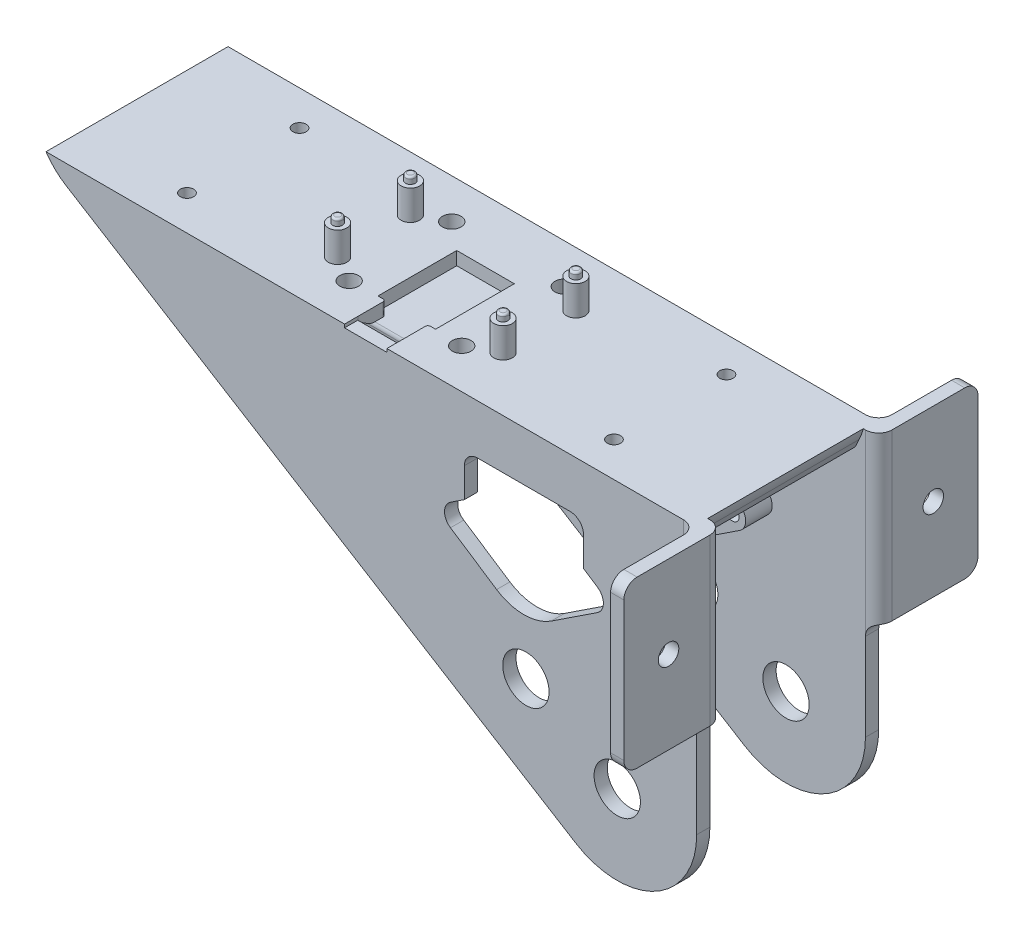
SolidWorks part; units mm, degrees
material "尼龙 101"
ref_plane "前视基准面" through (0, 0, 0) normal (0, 0, 1) x (1, 0, 0)
ref_plane "上视基准面" through (0, 0, 0) normal (0, 1, 0) x (1, 0, 0)
ref_plane "右视基准面" through (0, 0, 0) normal (1, 0, 0) x (0, 0, -1)
other "Configuration Table"
sketch "草图1" plane through (0, 0, 0) normal (0, 1, 0) x (1, 0, 0)
  line L1 (-50, 12.75) -> (50, 12.75)
  line L2 (-50, 12.75) -> (-50, -12.75)
  line L3 (-50, -12.75) -> (50, -12.75)
  line L4 (50, 12.75) -> (50, -12.75)
  line L5 (-50, 12.75) -> (50, -12.75) construction
  line L6 (-50, -12.75) -> (50, 12.75) construction
  point P0 (0, 0)
  dimension "D1" = 100
  dimension "D2" = 25.5
extrude "凸台-拉伸1" add sketch "草图1" along normal blind 3
sketch "草图2" plane through (0, 3, 0) normal (0, 1, 0) x (1, 0, 0)
  line L0 (0, 0) -> (0, 5.35) construction
  line L1 (-5.35, 5.35) -> (5.35, 5.35)
  line L2 (5.35, 5.35) -> (5.35, -7.55)
  line L3 (5.35, -7.55) -> (4.35, -7.55)
  line L4 (4.35, -7.55) -> (4.35, 4.35)
  line L5 (4.35, 4.35) -> (-4.35, 4.35)
  line L6 (-4.35, -7.55) -> (-4.35, 4.35)
  line L7 (-5.35, -7.55) -> (-4.35, -7.55)
  line L8 (-5.35, 5.35) -> (-5.35, -7.55)
  point P9 (0, 4.35)
  dimension "D1" = 8.7
  dimension "D2" = 11.9
  dimension "D3" = 4.35
  dimension "D4" = 1
  dimension "D5" = 1
extrude "凸台-拉伸2" add sketch "草图2" along normal blind 1.5
sketch "草图5" plane through (0, 3, 0) normal (0, 1, 0) x (1, 0, 0)
  line L0 (0, 12.75) -> (0, 0) construction
  line L1 (50, 12.75) -> (-50, 12.75) construction
  line L2 (0, 0) -> (50, 0) construction
  line L3 (50, -12.75) -> (50, 12.75) construction
  circle A0 centre (12.5, 5.5) radius 1.4
  circle A1 centre (12.5, -5.5) radius 1.4
  circle A2 centre (-12.5, -5.5) radius 1.4
  circle A3 centre (-12.5, 5.5) radius 1.4
  dimension "D1" = 2.8
  dimension "D2" = 25
  dimension "D3" = 11
extrude "凸台-拉伸3" add sketch "草图5" along normal blind 4.5
sketch "草图6" plane through (0, 7.5, 0) normal (0, 1, 0) x (1, 0, 0)
  circle A0 centre (-12.5, -5.5) radius 0.725
  circle A1 centre (-12.5, 5.5) radius 0.725
  circle A2 centre (12.5, 5.5) radius 0.725
  circle A3 centre (12.5, -5.5) radius 0.725
  dimension "D1" = 1.45
extrude "凸台-拉伸4" add sketch "草图6" along normal blind 1
sketch "草图7" plane through (0, 3, 0) normal (0, 1, 0) x (1, 0, 0)
  line L0 (0, 0) -> (0, 12.75) construction
  line L1 (50, 12.75) -> (-50, 12.75) construction
  line L2 (0, 0) -> (50, 0) construction
  line L3 (50, -12.75) -> (50, 12.75) construction
  circle A0 centre (32.25, 8.5) radius 1
  circle A1 centre (-32.25, 8.5) radius 1
  circle A2 centre (-32.25, -8.5) radius 1
  circle A3 centre (32.25, -8.5) radius 1
  dimension "D1" = 2
  dimension "D2" = 17
  dimension "D3" = 64.5
extrude "切除-拉伸1" cut sketch "草图7" against normal blind 10
sketch "草图8" plane through (0, 0, 0) normal (0, -1, 0) x (1, 0, 0)
  circle A0 centre (-32.25, 8.5) radius 2
  circle A1 centre (32.25, 8.5) radius 2
  circle A2 centre (32.25, -8.5) radius 2
  circle A3 centre (-32.25, -8.5) radius 2
  dimension "D1" = 4
extrude "切除-拉伸2" cut sketch "草图8" against normal blind 1
fillet "圆角1" radius 2 4 edges at (-50, 1.5, -12.75) (50, 1.5, -12.75) (-50, 1.5, 12.75) (50, 1.5, 12.75)
sketch "草图9" plane through (0, 3, 0) normal (0, 1, 0) x (1, 0, 0)
  line L0 (0, 12.75) -> (0, 0) construction
  line L1 (48, 12.75) -> (-48, 12.75) construction
  line L2 (0, 0) -> (50, 0) construction
  line L3 (50, -10.75) -> (50, 10.75) construction
  circle A0 centre (8.5, 7.75) radius 2.65
  circle A1 centre (-8.5, 7.75) radius 2.65
  circle A2 centre (-8.5, -7.75) radius 2.65
  circle A3 centre (8.5, -7.75) radius 2.65
  dimension "D1" = 17
  dimension "D2" = 15.5
  dimension "D3" = 5.3
extrude "凸台-拉伸5" add sketch "草图9" along normal blind 3.5
sketch "草图11" plane through (0, 6.5, 0) normal (0, 1, 0) x (1, 0, 0)
  circle A0 centre (-8.5, 7.75) radius 1.05
  circle A1 centre (-8.5, -7.75) radius 1.05
  circle A2 centre (8.5, -7.75) radius 1.05
  circle A3 centre (8.5, 7.75) radius 1.05
  dimension "D1" = 2.1
extrude "切除-拉伸4" cut sketch "草图11" against normal blind 100
sketch "草图12" plane through (0, 6.5, 0) normal (0, 1, 0) x (1, 0, 0)
  circle A0 centre (-8.5, 7.75) radius 1.41
  circle A1 centre (8.5, 7.75) radius 1.41
  circle A2 centre (-8.5, -7.75) radius 1.41
  circle A3 centre (8.5, -7.75) radius 1.41
  dimension "D1" = 2.82
extrude "切除-拉伸5" cut sketch "草图12" against normal blind 5.5
fillet "圆角2" radius 0.3 4 edges at (12.5, 8.5, -4.775) (12.5, 8.5, 6.225) (-12.5, 8.5, 6.225) (-12.5, 8.5, -4.775)
sketch "草图15" plane through (0, 3, 0) normal (0, 1, 0) x (1, 0, 0)
  line L0 (0, 0) -> (0, 12.75) construction
  line L1 (48, 12.75) -> (-48, 12.75) construction
  line L2 (-4.35, 4.35) -> (4.35, 4.35)
  line L3 (4.35, 4.35) -> (4.35, -7.55)
  line L4 (4.35, -7.55) -> (3.2, -7.55)
  line L5 (3.2, -7.55) -> (3.2, -12.75)
  line L6 (-48, -12.75) -> (48, -12.75) construction
  line L7 (3.2, -12.75) -> (-3.2, -12.75)
  line L8 (-3.2, -7.55) -> (-3.2, -12.75)
  line L9 (-4.35, -7.55) -> (-3.2, -7.55)
  line L10 (-4.35, 4.35) -> (-4.35, -7.55)
  line L11 (4.35, 4.35) -> (4.35, -7.55) construction
  point P14 (0, -12.75)
  point P17 (0, 4.35)
  dimension "D1" = 6.4
extrude "切除-拉伸8" cut sketch "草图15" against normal blind 2
sketch "草图17" plane through (0, 4.5, 0) normal (0, 1, 0) x (1, 0, 0)
  line L8 (-4.35, -7.55) -> (-4.35, 4.35)
  line L9 (-4.35, 4.35) -> (4.35, 4.35)
  line L10 (4.35, 4.35) -> (4.35, -7.55)
  line L11 (4.35, -7.55) -> (5.35, -7.55)
  line L12 (5.35, -7.55) -> (5.35, 5.35)
  line L13 (5.35, 5.35) -> (-5.35, 5.35)
  line L14 (-5.35, 5.35) -> (-5.35, -7.55)
  line L15 (-5.35, -7.55) -> (-4.35, -7.55)
  line L16 (-4.35, -7.55) -> (-4.35, 4.35)
  line L17 (-4.35, 4.35) -> (4.35, 4.35)
  line L18 (4.35, 4.35) -> (4.35, -7.55)
  line L19 (4.35, -7.55) -> (5.35, -7.55)
  line L20 (5.35, -7.55) -> (5.35, 5.35)
  line L21 (5.35, 5.35) -> (-5.35, 5.35)
  line L22 (-5.35, 5.35) -> (-5.35, -7.55)
  line L23 (-5.35, -7.55) -> (-4.35, -7.55)
  dimension "D1" = 0
extrude "切除-拉伸9" cut sketch "草图17" against normal blind 1.5
sketch "草图18" plane through (3.2, 0, 0) normal (-1, 0, 0) x (0, 0, 1)
  line L0 (12.75, 1) -> (9.75, 1)
  line L2 (12.75, 1) -> (12.75, 3) construction
  line L3 (12.75, 2.6) -> (12.75, 1)
  line L5 (12.75, 3) -> (12.75, 0) construction
  line L6 (12.75, 2.6) -> (12.25, 2.6)
  line L7 (12.25, 2.6) -> (9.75, 1)
  line L8 (12.75, 3) -> (10.75, 3) construction
  dimension "D1" = 3
  dimension "D2" = 0.4
  dimension "D3" = 0.5
extrude "凸台-拉伸6" add sketch "草图18" along normal up to surface (6.4 mm away) up to face at (-3.2, 2, 10.15)
fillet "圆角3" radius 2 1 edges at (0, 1, 9.75)
fillet "圆角5" radius 1 1 edges at (0, 2.6, 12.25)
fillet "圆角6" radius 0.4 2 edges at (3.2, 2, 7.55) (-3.2, 2, 7.55)
sketch "草图23" plane through (0, 3, 0) normal (0, 1, 0) x (1, 0, 0)
  line L0 (0, 0) -> (0, 14.3059) construction
  line L1 (0, 0) -> (9.7311, 0) construction
  line L2 (9.7311, -0.4768) -> (9.7311, 0.4767) construction
  line L3 (6.497, 0) -> (-6.497, 0) construction
  circle A0 centre (-8.5, 7.75) radius 2.839
  circle A1 centre (8.5, 7.75) radius 2.839
  circle A2 centre (8.5, -7.75) radius 2.839
  circle A3 centre (-8.5, -7.75) radius 2.839
extrude "切除-拉伸11" cut sketch "草图23" along normal blind 5
ref_plane "基准面1" through (0, 0, 0) normal (0, 0, -1) x (-1, 0, 0)
sketch "草图26" plane through (0, 0, -12.75) normal (0, 0, -1) x (-1, 0, 0)
  line L0 (50, 3) -> (-47.2265, -57.0098)
  line L1 (-50, 3) -> (-50, -58.7217)
  line L3 (-47.2265, -57.0098) -> (-50, -58.7217)
  line L4 (-50, 3) -> (50, 3)
  line L6 (-51, 3) -> (49.4801, 3) construction
  line L7 (-48, 3) -> (-50, 3) construction
extrude "凸台-拉伸12" add sketch "草图26" against normal mid plane 2
ref_plane "基准面2" through (0, 0, -11.75) normal (0, 0, -1) x (-1, 0, 0)
ref_plane "基准面3" through (0, 0, 0) normal (0, 0, 1) x (1, 0, 0)
mirror "镜向1" about plane through (0, 0, 0) normal (0, 0, 1) of "凸台-拉伸12"
sketch "草图34" plane through (0, 0, -13.75) normal (0, 0, -1) x (-1, 0, 0)
  line L0 (50, 15.0087) -> (50, 8.5792)
  line L1 (50, 8.5792) -> (50, 13) construction
  line L2 (45.2523, 0.0696) -> (38.3449, -4.1938)
  line L3 (-50, -58.7217) -> (50, 3) construction
  line L4 (50, 15.0087) -> (52.8395, -4.7654)
  line L5 (52.8395, -4.7654) -> (38.3449, -4.1938)
  arc A0 (45.2523, 0.0696) -> (50, 8.5792) centre (40, 8.5792) ccw
  point P12 (50, 3)
  dimension "D1" = 10
extrude "切除-拉伸20" cut sketch "草图34" against normal up to surface (27.5 mm away) up to face at (16.6667, -17.5739, 13.75)
sketch "草图35" plane through (0, 0, -11.75) normal (0, 0, 1) x (1, 0, 0)
  line L9 (50, 10.631) -> (50, 5.5397)
  line L10 (57.0725, -23.7563) -> (50, 10.631)
  line L11 (33.7407, -30.9984) -> (57.0725, -23.7563)
  line L12 (49.0355, 1.255) -> (33.7407, -30.9984)
  arc A2 (49.0355, 1.255) -> (50, 5.5397) centre (40, 5.5397) ccw
extrude "切除-拉伸21" cut sketch "草图35" along normal up to surface (23.5 mm away) up to face at (30.8649, -10.5443, 11.75)
sketch "草图37" plane through (0, 0, -13.75) normal (0, 0, -1) x (-1, 0, 0)
  line L0 (-50, -58.7217) -> (-31.6973, -47.425)
  line L1 (-50, 3) -> (-50, -58.7217) construction
  line L2 (-50, -58.7217) -> (-50, -37.2134)
  line L3 (-50, -58.7217) -> (45.2523, 0.0696) construction
  arc A0 (-50, -37.2134) -> (-31.6973, -47.425) centre (-38, -37.2134) ccw
  dimension "D1" = 12
  dimension "D2" = 12
extrude "切除-拉伸22" cut sketch "草图37" against normal blind 30
sketch "草图38" plane through (0, 0, 13.75) normal (0, 0, 1) x (1, 0, 0)
  circle A0 centre (38, -37.2134) radius 3.5
extrude "切除-拉伸23" cut sketch "草图38" against normal blind 50
sketch "草图40" plane through (0, 0, 13.75) normal (0, 0, 1) x (1, 0, 0)
  circle A0 centre (24.2023, -29.6951) radius 3.5
extrude "切除-拉伸24" cut sketch "草图40" against normal blind 50
sketch "草图41" plane through (0, 0, 13.75) normal (0, 0, 1) x (1, 0, 0)
  circle A0 centre (23.9052, -13.9776) radius 3.5
extrude "切除-拉伸25" cut sketch "草图41" against normal blind 50
sketch "草图43" plane through (0, 0, 13.75) normal (0, 0, 1) x (1, 0, 0)
  line L0 (28.0302, -7.7139) -> (35.0052, -12.3073) construction
  line L1 (35.0052, -15.648) -> (28.0302, -20.2414) construction
  line L2 (19.7802, -20.2414) -> (12.8052, -15.648) construction
  line L3 (12.8052, -12.3073) -> (19.7802, -7.7139) construction
  line L4 (28.0302, -7.7139) -> (35.0052, -12.3073)
  line L5 (35.0052, -15.648) -> (28.0302, -20.2414)
  line L6 (19.7802, -20.2414) -> (12.8052, -15.648)
  line L7 (12.8052, -12.3073) -> (19.7802, -7.7139)
  arc A0 (35.0052, -15.648) -> (35.0052, -12.3073) centre (33.9052, -13.9776) ccw construction
  arc A1 (12.8052, -12.3073) -> (12.8052, -15.648) centre (13.9052, -13.9776) ccw construction
  circle A2 centre (23.9052, -13.9776) radius 7.5 construction
  arc A3 (35.0052, -15.648) -> (35.0052, -12.3073) centre (33.9052, -13.9776) ccw
  arc A4 (12.8052, -12.3073) -> (12.8052, -15.648) centre (13.9052, -13.9776) ccw
  arc A5 (19.7802, -20.2414) -> (28.0302, -20.2414) centre (23.9052, -13.9776) ccw
  arc A6 (28.0302, -7.7139) -> (19.7802, -7.7139) centre (23.9052, -13.9776) ccw
extrude "切除-拉伸26" cut sketch "草图43" against normal blind 20
sketch "草图44" plane through (0, 0, -13.75) normal (0, 0, -1) x (-1, 0, 0)
  circle A0 centre (-23.9052, -13.9776) radius 3.5
sketch "草图45" plane through (0, 0, -11.75) normal (0, 0, 1) x (1, 0, 0)
  line L4 (19.7802, -7.7139) -> (12.8052, -12.3073)
  line L5 (35.0052, -12.3073) -> (28.0302, -7.7139)
  line L6 (28.0302, -20.2414) -> (35.0052, -15.648)
  line L7 (12.8052, -15.648) -> (19.7802, -20.2414)
  line L8 (19.7802, -7.7139) -> (12.8052, -12.3073)
  line L9 (35.0052, -12.3073) -> (28.0302, -7.7139)
  line L10 (28.0302, -20.2414) -> (35.0052, -15.648)
  line L13 (12.8052, -15.648) -> (19.7802, -20.2414)
  circle A1 centre (23.9052, -13.9776) radius 4
  arc A4 (28.0302, -7.7139) -> (19.7802, -7.7139) centre (23.9052, -13.9776) ccw
  arc A5 (35.0052, -15.648) -> (35.0052, -12.3073) centre (33.9052, -13.9776) ccw
  arc A6 (19.7802, -20.2414) -> (28.0302, -20.2414) centre (23.9052, -13.9776) ccw
  arc A8 (28.0302, -7.7139) -> (19.7802, -7.7139) centre (23.9052, -13.9776) ccw
  arc A9 (35.0052, -15.648) -> (35.0052, -12.3073) centre (33.9052, -13.9776) ccw
  arc A15 (19.7802, -20.2414) -> (28.0302, -20.2414) centre (23.9052, -13.9776) ccw
  arc A17 (12.8052, -12.3073) -> (12.8052, -15.648) centre (13.9052, -13.9776) ccw
  arc A18 (12.8052, -12.3073) -> (12.8052, -15.648) centre (13.9052, -13.9776) ccw
  dimension "D1" = 0
extrude "凸台-拉伸13" add sketch "草图45" along normal blind 4
ref_plane "基准面4" through (28.0302, -20.2414, -7.75) normal (-0.8352, -0.55, 0) x (0, 0, 1)
sketch "草图47" plane through (0, 0, -7.75) normal (0, 0, 1) x (1, 0, 0)
  circle A0 centre (33.9052, -13.9776) radius 1 construction
  circle A1 centre (13.9052, -13.9776) radius 1 construction
  circle A2 centre (33.9052, -13.9776) radius 1
  circle A3 centre (13.9052, -13.9776) radius 1
extrude "切除-拉伸29" cut sketch "草图47" against normal blind 4
sketch "草图48" plane through (0, 0, 13.75) normal (0, 0, 1) x (1, 0, 0)
  line L0 (51, 3) -> (-49.4801, 3) construction
  line L2 (4.35, 2.5) -> (-4.35, 2.5) construction
  line L4 (3.1976, 3) -> (-3.1988, 3)
  line L6 (3.1976, 2.5) -> (-3.1988, 2.5)
  line L8 (-3.1988, 3) -> (-3.1988, 2.5)
  line L9 (3.1976, 2.5) -> (3.1976, 3)
extrude "切除-拉伸30" cut sketch "草图48" against normal blind 5
sketch "草图49" plane through (0, 0, 13.75) normal (0, 0, 1) x (1, 0, 0)
  line L1 (16.9052, -4.4776) -> (30.9052, -4.4776)
  line L2 (14.9052, -6.4776) -> (14.9052, -11.4776)
  line L3 (14.9052, -11.4776) -> (32.9052, -11.4776)
  line L4 (32.9052, -6.4776) -> (32.9052, -11.4776)
  arc A0 (28.0302, -7.7139) -> (19.7802, -7.7139) centre (23.9052, -13.9776) ccw construction
  arc A1 (32.9052, -6.4776) -> (30.9052, -4.4776) centre (30.9052, -6.4776) ccw
  arc A2 (16.9052, -4.4776) -> (14.9052, -6.4776) centre (16.9052, -6.4776) ccw
  point P8 (23.9052, -6.4776)
  dimension "D2" = 2
  dimension "D5" = 2
  dimension "D1" = 9
  dimension "D3" = 9
  dimension "D4" = 7
extrude "切除-拉伸31" cut sketch "草图49" against normal blind 10
sketch "草图50" plane through (50, 0, 0) normal (1, 0, 0) x (0, 0, -1)
  line L0 (0, 0) -> (0, -12.9975) construction
  line L1 (11.75, 3) -> (26.75, 3)
  line L2 (11.75, 3) -> (11.75, -22)
  line L3 (11.75, -22) -> (26.75, -22)
  line L4 (26.75, 3) -> (26.75, -22)
  line L5 (-26.75, 3) -> (-26.75, -22)
  line L6 (-11.75, -22) -> (-26.75, -22)
  line L7 (-11.75, 3) -> (-11.75, -22)
  line L8 (-11.75, 3) -> (-26.75, 3)
  circle A0 centre (-20, -9.5) radius 1.55
  circle A1 centre (20, -9.5) radius 1.55
  point P8 (20, -9.5)
  point P14 (-20, -9.5)
  dimension "D1" = 12.5
  dimension "D2" = 40
extrude "凸台-拉伸14" add sketch "草图50" along normal blind 2
fillet "圆角8" radius 2 6 edges at (51, 3, -26.75) (51, -22, -26.75) (51, -22, 26.75) (51, 3, 26.75) (50, -9.5, 13.75) (50, -9.5, -13.75)
fillet "圆角9" radius 2 2 edges at (50, -22, 12.75) (50, -22, -12.75)
fillet "圆角10" radius 2 2 edges at (52, -9.5, -11.75) (52, -9.5, 11.75)
